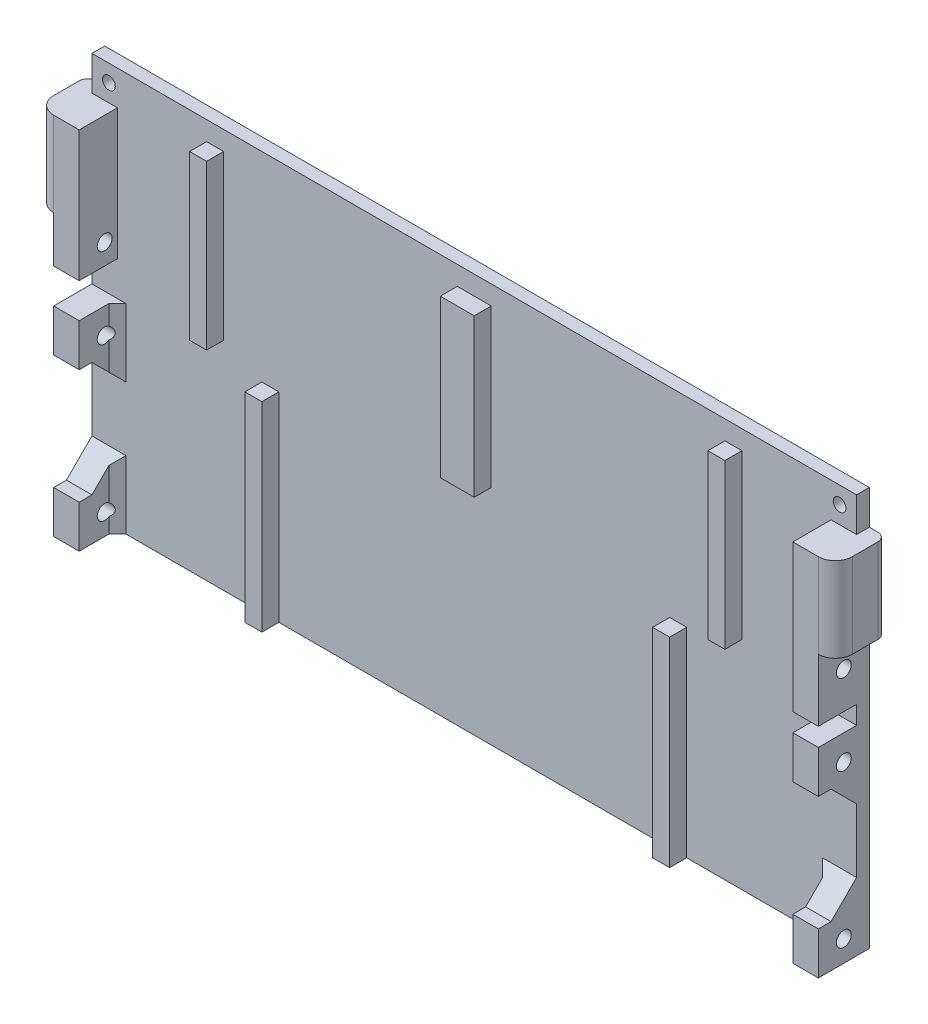
SolidWorks part; units mm, degrees
material "АБС-2020, черный"
ref_plane "Спереди" through (0, 0, 0) normal (0, 0, 1) x (1, 0, 0)
ref_plane "Сверху" through (0, 0, 0) normal (0, 1, 0) x (1, 0, 0)
ref_plane "Справа" through (0, 0, 0) normal (1, 0, 0) x (0, 0, -1)
other "Configuration Table"
sketch "Эскиз1" plane through (0, 0, 0) normal (0, 0, 1) x (1, 0, 0)
  line L1 (0, 0) -> (180, 0)
  line L2 (0, 0) -> (0, -94)
  line L3 (0, -94) -> (180, -94)
  line L4 (180, 0) -> (180, -94)
  dimension "D1" = 94
  dimension "D2" = 180
extrude "Бобышка-Вытянуть1" add sketch "Эскиз1" along normal blind 3
sketch "Эскиз2" plane through (0, 0, 3) normal (0, 0, 1) x (1, 0, 0)
  line L0 (0, 0) -> (0, -94) construction
  line L1 (0, -94) -> (6, -94)
  line L2 (0, -94) -> (0, -84)
  line L3 (0, -84) -> (6, -84)
  line L4 (6, -94) -> (6, -84)
  line L5 (180, -94) -> (174, -94)
  line L6 (180, -94) -> (180, -84)
  line L7 (180, -84) -> (174, -84)
  line L8 (174, -94) -> (174, -84)
  line L9 (0, -47) -> (6, -47)
  line L10 (0, -47) -> (0, -57)
  line L11 (0, -57) -> (6, -57)
  line L12 (6, -47) -> (6, -57)
  line L13 (180, -94) -> (180, 0) construction
  line L14 (180, -47) -> (174, -47)
  line L15 (180, -47) -> (180, -57)
  line L16 (180, -57) -> (174, -57)
  line L17 (174, -47) -> (174, -57)
  line L18 (0, -94) -> (180, -94) construction
  line L19 (180, 0) -> (0, 0) construction
  line L20 (180, -8.1) -> (174, -8.1)
  line L21 (180, -8.1) -> (180, -42.7)
  line L22 (180, -42.7) -> (174, -42.7)
  line L23 (174, -8.1) -> (174, -42.7)
  line L24 (0, -8.1) -> (6, -8.1)
  line L25 (0, -8.1) -> (0, -38.854)
  line L26 (0, -38.854) -> (6, -38.854)
  line L27 (6, -8.1) -> (6, -38.854)
  point P34 (0, 0)
  point P37 (0, 0)
  dimension "D1" = 10
  dimension "D2" = 6
  dimension "D3" = 10
  dimension "D4" = 6
  dimension "D5" = 47
  dimension "D6" = 6
  dimension "D7" = 6
  dimension "D8" = 47
  dimension "D9" = 10
  dimension "D10" = 10
  dimension "D11" = 4.3
  dimension "D12" = 8.1
  dimension "D13" = 8.1
extrude "Бобышка-Вытянуть2" add sketch "Эскиз2" along normal blind 9
chamfer "Фаска2" distance 6 angle 45 2 edges at (3, -57, 3) (177, -57, 3)
chamfer "Фаска1" distance 6 angle 45 2 edges at (3, -84, 3) (177, -84, 3)
sketch "Эскиз3" plane through (180, 0, 0) normal (1, 0, 0) x (0, 0, -1)
  line L0 (0, -94) -> (0, 0) construction
  line L1 (-12, -94) -> (0, -94) construction
  line L2 (-3, 0) -> (0, 0) construction
  circle A0 centre (-6, -89) radius 1.75
  circle A1 centre (-6, -53) radius 1.75
  circle A2 centre (-6, -34) radius 1.75
  dimension "D1" = 3.5
  dimension "D4" = 3.5
  dimension "D7" = 3.5
  dimension "D2" = 6
  dimension "D3" = 5
  dimension "D5" = 36
  dimension "D6" = 34
extrude "Вырез-Вытянуть1" cut sketch "Эскиз3" against normal through all
sketch "Эскиз4" plane through (0, 0, 3) normal (0, 0, 1) x (1, 0, 0)
  line L0 (0, -84) -> (0, -94) construction
  line L1 (180, -94) -> (180, -84) construction
  line L2 (180, 0) -> (0, 0) construction
  circle A0 centre (4, -4) radius 1.5
  circle A1 centre (176, -4) radius 1.5
  dimension "D7" = 3
  dimension "D1" = 4
  dimension "D2" = 4
  dimension "D3" = 4
extrude "Вырез-Вытянуть2" cut sketch "Эскиз4" against normal through all
sketch "Эскиз5" plane through (0, 0, 3) normal (0, 0, 1) x (1, 0, 0)
  line L0 (6, -94) -> (174, -94) construction
  line L1 (40, -47) -> (44, -47)
  line L2 (40, -47) -> (40, -94)
  line L3 (40, -94) -> (44, -94)
  line L4 (44, -47) -> (44, -94)
  line L5 (180, -78) -> (180, -63) construction
  line L6 (136, -47) -> (140, -47)
  line L7 (136, -47) -> (136, -94)
  line L8 (136, -94) -> (140, -94)
  line L9 (140, -47) -> (140, -94)
  line L10 (0, -63) -> (0, -78) construction
  line L11 (180, 0) -> (0, 0) construction
  line L13 (27, -4.5) -> (27, -43)
  line L14 (27, -43) -> (31, -43)
  line L15 (31, -4.5) -> (31, -43)
  line L16 (6, -47) -> (0, -47) construction
  line L18 (149, -4.5) -> (149, -43)
  line L19 (149, -43) -> (153, -43)
  line L20 (153, -4.5) -> (153, -43)
  line L21 (27, -4.5) -> (31, -4.5)
  line L22 (149, -4.5) -> (153, -4.5)
  line L23 (0, 0) -> (0, -8.1) construction
  line L24 (180, -47) -> (180, -42.7) construction
  line L26 (86, -4.5) -> (94, -4.5)
  line L27 (86, -4.5) -> (86, -41.5)
  line L28 (86, -41.5) -> (94, -41.5)
  line L29 (94, -4.5) -> (94, -41.5)
  dimension "D12" = 8
  dimension "D1" = 4
  dimension "D2" = 4
  dimension "D3" = 40
  dimension "D4" = 40
  dimension "D5" = 4
  dimension "D6" = 4
  dimension "D7" = 27
  dimension "D8" = 4
  dimension "D9" = 4.5
  dimension "D10" = 4
  dimension "D11" = 27
  dimension "D13" = 55
  dimension "D14" = 55
extrude "Бобышка-Вытянуть3" add sketch "Эскиз5" along normal blind 4
chamfer "Фаска3" distance 2 angle 45 4 edges at (174, -86, 3) (174, -55, 3) (6, -86, 3) (6, -55, 3)
sketch "Эскиз6" plane through (180, 0, 0) normal (1, 0, 0) x (0, 0, -1)
  line L0 (0, -94) -> (0, 0) construction
  line L1 (-12, -8.1) -> (0, -8.1)
  line L2 (-12, -8.1) -> (-12, -28)
  line L3 (-12, -28) -> (0, -28)
  line L4 (0, -8.1) -> (0, -28)
  line L5 (-3, 0) -> (0, 0) construction
  point P7 (0, 0)
  point P8 (0, 0)
  point P9 (0, 0)
  point P10 (0, 0)
  point P13 (-12, -8.1)
  dimension "D1" = 28
  dimension "D2" = 8.1
extrude "Бобышка-Вытянуть4" add sketch "Эскиз6" along normal blind 4
fillet "Скругление1" radius 4 1 edges at (184, -18.05, 12)
sketch "Эскиз7" plane through (0, 0, 0) normal (-1, 0, 0) x (0, 0, 1)
  line L0 (12, -8.1) -> (12, -38.854) construction
  line L1 (0, -8.1) -> (12, -8.1)
  line L2 (0, -8.1) -> (0, -28)
  line L3 (0, -28) -> (12, -28)
  line L4 (12, -8.1) -> (12, -28)
  line L5 (3, 0) -> (0, 0) construction
  point P7 (0, 0)
  point P8 (12, -8.1)
  dimension "D1" = 28
extrude "Бобышка-Вытянуть5" add sketch "Эскиз7" along normal blind 4
fillet "Скругление2" radius 4 1 edges at (-4, -18.05, 12)
fillet "Скругление3" radius 2 2 edges at (184, -18.05, 0) (-4, -18.05, 0)
